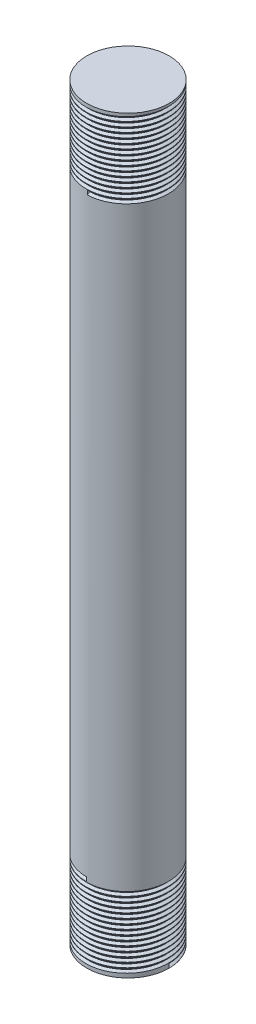
SolidWorks part; units mm, degrees
ref_plane "Front Plane" through (0, 0, 0) normal (0, 0, 1) x (1, 0, 0)
ref_plane "Top Plane" through (0, 0, 0) normal (0, 1, 0) x (1, 0, 0)
ref_plane "Right Plane" through (0, 0, 0) normal (1, 0, 0) x (0, 0, -1)
sketch "Sketch1" plane through (0, 0, 0) normal (0, 0, 1) x (1, 0, 0)
  line L0 (0, -54.5876) -> (0, -104.5876)
  dimension "D1" = 50
revolve "Revolve-Thin1" add sketch "Sketch1" angle 360 about L0 wall 2.75
thread "Thread1" pitch 0.3175 method cut profile "Thread Profile1" start angle 0, offset 0, length 5, pitch 0.3175, diameter 5.5
ref_plane "Plane1" through (-2.75, -54.5876, 0) normal (0, 0, 1) x (-1, 0, 0)
sketch "Thread Profile1" plane through (-2.75, -54.5876, 0) normal (0, 0, 1) x (-1, 0, 0)
  line L0 (0, 0) -> (0, 0.3175) construction
  line L11 (0, 0) -> (0, 0.2778)
  line L12 (0, 0.2778) -> (-0.1719, 0.1786)
  line L13 (-0.1719, 0.1786) -> (-0.1719, 0.0992)
  line L15 (-0.1719, 0.0992) -> (0, 0)
  line L17 (-0.1719, 0.1389) -> (0, 0.1389) construction
  point P2 (0, 0)
  dimension "Pitch" = 0.3175
  dimension "Profile_Angle" = 60
  dimension "Profile_Land" = 0.0794
  dimension "Profile_Height" = 0.1719
thread "Thread2" pitch 0.3175 method cut profile "Thread Profile2" start angle 0, offset 0, length 5, pitch 0.3175, diameter 5.5
ref_plane "Plane2" through (2.75, -104.5876, 0) normal (0, 0, 1) x (1, 0, 0)
sketch "Thread Profile2" plane through (2.75, -104.5876, 0) normal (0, 0, 1) x (1, 0, 0)
  line L0 (0, 0) -> (0, 0.3175) construction
  line L11 (0, 0) -> (0, 0.2778)
  line L12 (0, 0.2778) -> (-0.1719, 0.1786)
  line L13 (-0.1719, 0.1786) -> (-0.1719, 0.0992)
  line L15 (-0.1719, 0.0992) -> (0, 0)
  line L17 (-0.1719, 0.1389) -> (0, 0.1389) construction
  point P2 (0, 0)
  dimension "Pitch" = 0.3175
  dimension "Profile_Angle" = 60
  dimension "Profile_Land" = 0.0794
  dimension "Profile_Height" = 0.1719
